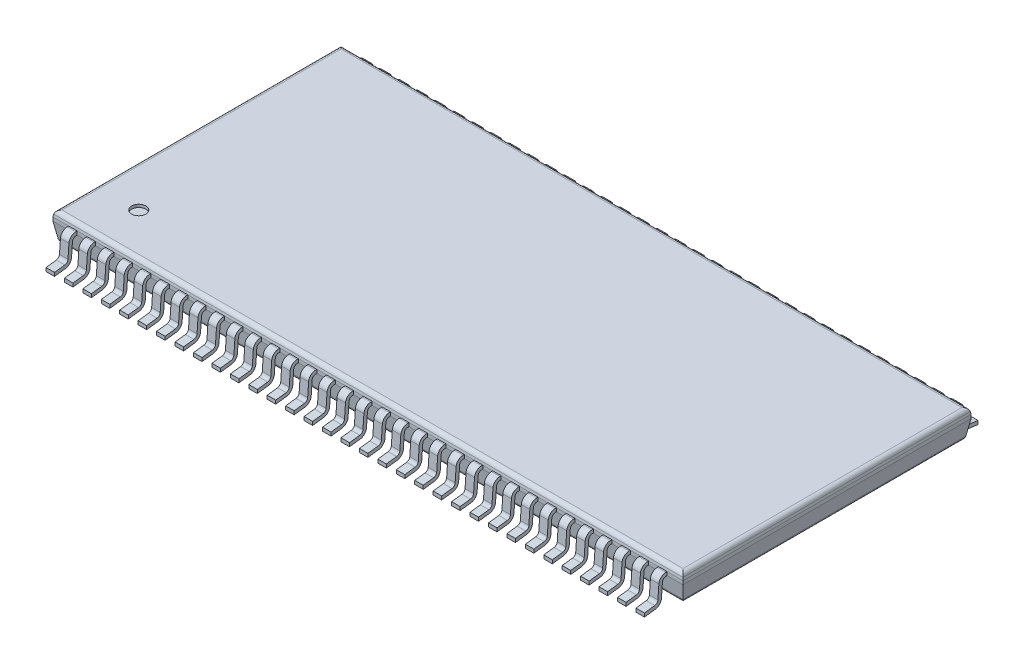
SolidWorks part; units mm, degrees
ref_plane "Front" through (0, 0, 0) normal (0, 0, 1) x (1, 0, 0)
ref_plane "Top" through (0, 0, 0) normal (0, 1, 0) x (1, 0, 0)
ref_plane "Right" through (0, 0, 0) normal (1, 0, 0) x (0, 0, -1)
sketch "Sketch1" plane through (0, 0, 0) normal (0, 1, 0) x (1, 0, 0)
  line L0 (-11.11, -5.08) -> (11.11, 5.08) construction
  line L1 (-11.11, 5.08) -> (11.11, 5.08)
  line L2 (-11.11, 5.08) -> (-11.11, -5.08)
  line L3 (-11.11, -5.08) -> (11.11, -5.08)
  line L4 (11.11, 5.08) -> (11.11, -5.08)
  dimension "D1" = 22.22
  dimension "D2" = 10.16
extrude "Extrude1" add sketch "Sketch1" along normal mid plane 1
chamfer "Chamfer3" distance 0.21 distance2 0.037 4 edges at (0, 0.5, -5.08) (11.11, 0.5, 0) (0, 0.5, 5.08) (-11.11, 0.5, 0) first distance on face at (0, 0, -5.08) first distance on face at (11.11, 0, 0) first distance on face at (0, 0, 5.08) first distance on face at (-11.11, 0, 0)
chamfer "Chamfer4" distance 0.117 distance2 0.665 4 edges at (0, -0.5, 5.08) (11.11, -0.5, 0) (0, -0.5, -5.08) (-11.11, -0.5, 0) first distance on face at (0, -0.5, 0)
fillet "Fillet1" radius 0.15 8 edges at (0, 0.5, 5.043) (-11.073, 0.5, 0) (0, 0.5, -5.043) (11.073, 0.5, 0) (0, -0.5, -4.963) (-10.993, -0.5, 0) (0, -0.5, 4.963) (10.993, -0.5, 0)
sketch "Sketch4" plane through (0, 0.5, 0) normal (0, 1, 0) x (-1, 0, 0)
  circle A0 centre (9.5948, 3.5648) radius 0.25
  dimension "D3" = 0.5
  dimension "D1" = 1.5
  dimension "D2" = 1.5
extrude "Cut-Extrude1" cut sketch "Sketch4" against normal blind 0.1
ref_plane "Plane1" through (-11.11, 0, 0) normal (1, 0, 0) x (0, 0, -1)
ref_plane "Plane2" through (-10.4, 0, 0) normal (1, 0, 0) x (0, 0, -1)
sketch "Sketch5" plane through (-10.4, 0, 0) normal (1, 0, 0) x (0, 0, -1)
  line L0 (-5.08, 0.165) -> (-5.1223, 0.165)
  line L1 (-5.88, -0.7) -> (-5.88, -0.575)
  line L2 (-5.08, 0.29) -> (-5.1223, 0.29)
  line L3 (-5.4995, -0.6542) -> (-5.88, -0.7)
  line L4 (-5.88, -0.575) -> (-5.5145, -0.5301)
  line L5 (-5.4047, -0.4147) -> (-5.3717, 0.0574)
  line L6 (-4.9171, 0.5) -> (4.9171, 0.5) construction
  line L7 (-5.247, 0.0487) -> (-5.28, -0.4235)
  line L8 (-5.08, 0.165) -> (-5.08, 0.29)
  line L9 (-5.28, -0.4235) -> (-5.28, -0.1868) construction
  line L10 (-5.08, 0.165) -> (5.08, 0.165) construction
  line L11 (-4.8371, -0.5) -> (-6.2321, -0.5) construction
  arc A0 (-5.1223, 0.29) -> (-5.3717, 0.0574) centre (-5.1223, 0.04) ccw
  arc A1 (-5.1223, 0.165) -> (-5.247, 0.0487) centre (-5.1223, 0.04) ccw
  arc A2 (-5.28, -0.4235) -> (-5.4995, -0.6542) centre (-5.5294, -0.406) cw
  arc A3 (-5.4047, -0.4147) -> (-5.5145, -0.5301) centre (-5.5294, -0.406) cw
  dimension "D1" = 0.25
  dimension "D2" = 0.25
  dimension "D4" = 0.8
  dimension "D3" = 0.125
  dimension "D5" = 1.2
  dimension "D6" = 4
  dimension "D7" = 0.6
  dimension "D8" = 7
extrude "Extrude2" add sketch "Sketch5" along normal mid plane 0.3
pattern_linear "LPattern1" count 33 spacing 0.65 along (1, 0, 0) of "Extrude2"
mirror "Mirror1" about plane through (0, 0, 0) normal (0, 0, 1) of "LPattern1"
